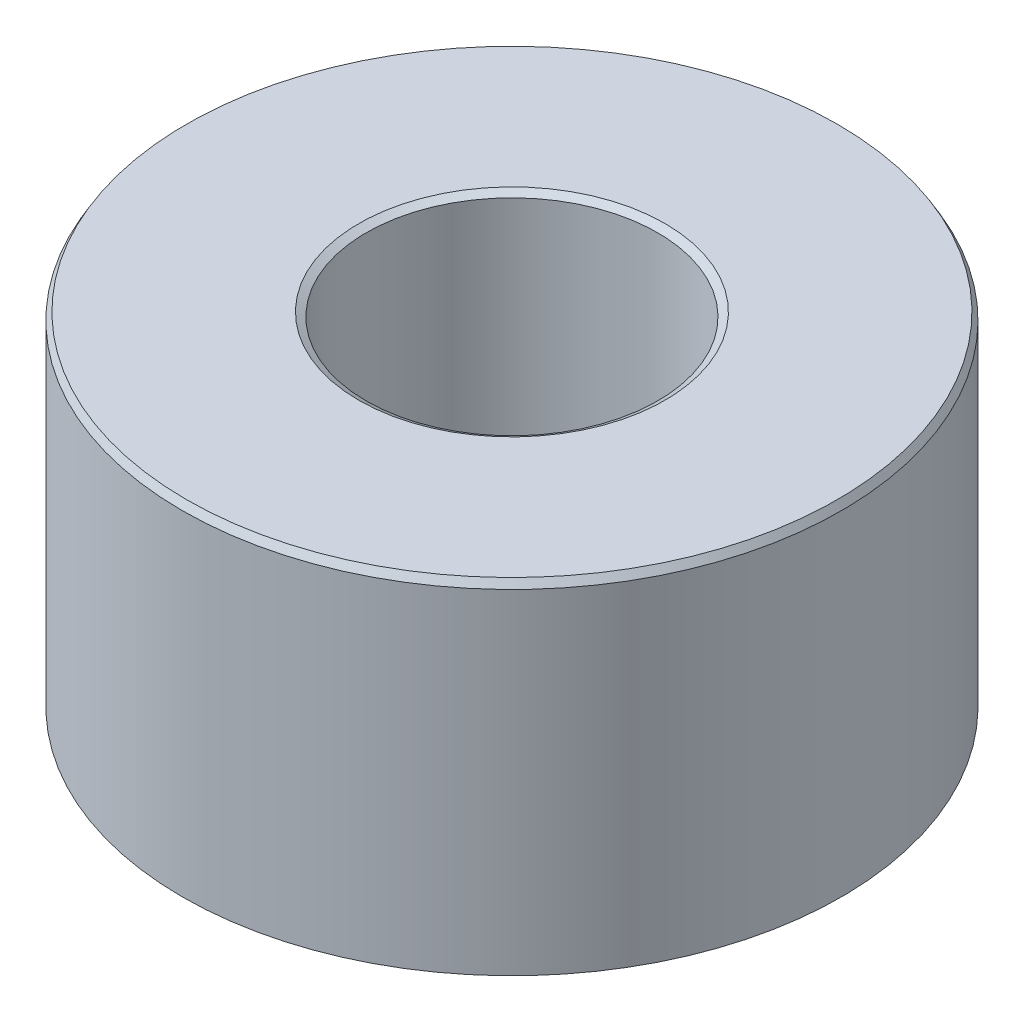
SolidWorks part; units mm, degrees
ref_plane "Front Plane" through (0, 0, 0) normal (0, 0, 1) x (1, 0, 0)
ref_plane "Top Plane" through (0, 0, 0) normal (0, 1, 0) x (1, 0, 0)
ref_plane "Right Plane" through (0, 0, 0) normal (1, 0, 0) x (0, 0, -1)
sketch "Sketch1" plane through (0, 0, 0) normal (0, 1, 0) x (1, 0, 0)
  circle A0 centre (0, 0) radius 42.5
  dimension "SLEEVE_OD" = 85
extrude "Boss-Extrude1" add sketch "Sketch1" along normal blind 44.6371
sketch "Sketch2" plane through (0, 0, 0) normal (0, 1, 0) x (1, 0, 0)
  circle A0 centre (0, 0) radius 18.793
  dimension "BORE_D" = 37.5859
extrude "Cut-Extrude1" cut sketch "Sketch2" along normal through all
chamfer "Chamfer1" distance 0.9501 angle 30 4 edges at (0, 44.6371, 18.793) (0, 0, 18.793) (0, 0, 42.5) (0, 44.6371, 42.5) first distance on face at (0, 44.6371, 18.793) first distance on face at (0, 0, 18.793) first distance on face at (0, 44.6371, 42.5)
